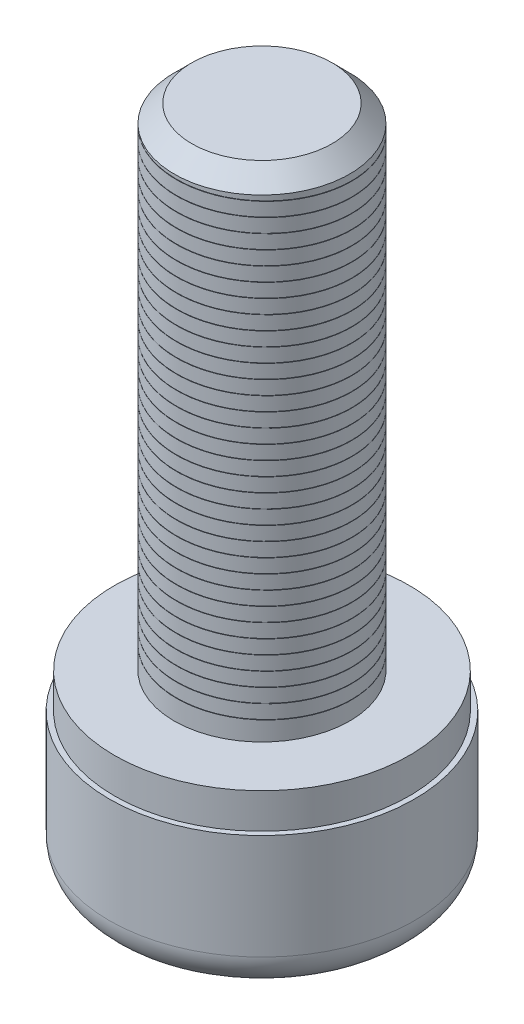
SolidWorks part; units mm, degrees
ref_plane "Спереди" through (0, 0, 0) normal (0, 0, 1) x (1, 0, 0)
ref_plane "Сверху" through (0, 0, 0) normal (0, 1, 0) x (1, 0, 0)
ref_plane "Справа" through (0, 0, 0) normal (1, 0, 0) x (0, 0, -1)
sketch "Эскиз1" plane through (0, 0, 0) normal (0, 1, 0) x (1, 0, 0)
  circle A0 centre (0, 0) radius 4.35
  dimension "D1" = 8.7
extrude "Бобышка-Вытянуть1" add sketch "Эскиз1" along normal blind 5
sketch "Эскиз2" plane through (0, 5, 0) normal (0, 1, 0) x (1, 0, 0)
  circle A0 centre (0, 0) radius 2.5
  dimension "D1" = 5
extrude "Бобышка-Вытянуть2" add sketch "Эскиз2" along normal blind 14
chamfer "Фаска1" distance 0.5 angle 45 1 edges at (0, 19, 2.5)
sketch "Эскиз3" plane through (0, 0, 0) normal (0, -1, 0) x (1, 0, 0)
  line L1 (1.9892, -1.1731) -> (2.0106, 1.1362)
  line L2 (2.0106, 1.1362) -> (0.0214, 2.3093)
  line L3 (0.0214, 2.3093) -> (-1.9892, 1.1731)
  line L4 (-1.9892, 1.1731) -> (-2.0106, -1.1362)
  line L5 (-2.0106, -1.1362) -> (-0.0214, -2.3093)
  line L6 (-0.0214, -2.3093) -> (1.9892, -1.1731)
  circle A0 centre (0, 0) radius 2 construction
  dimension "D1" = 4
extrude "Вырез-Вытянуть1" cut sketch "Эскиз3" against normal blind 2.5
fillet "Скругление1" radius 1 1 edges at (0, 0, 4.35)
sketch "Эскиз4" plane through (0, 5, 0) normal (0, 1, 0) x (1, 0, 0)
  circle A0 centre (0, 0) radius 4.2
  circle A1 centre (0, 0) radius 4.35
  dimension "D1" = 8.4
extrude "Вырез-Вытянуть3" cut sketch "Эскиз4" against normal blind 1
sketch "Эскиз7" plane through (0, 19, 0) normal (0, 1, 0) x (1, 0, 0)
  circle A0 centre (0, 0) radius 2.5
ref_plane "Плоскость2" through (0, 18.5, 0) normal (0, -1, 0) x (-1, 0, 0)
sketch "Эскиз8" plane through (0, 18.5, 0) normal (0, -1, 0) x (-1, 0, 0)
  circle A0 centre (0, 0) radius 2.5
curve "Спираль2" pitch 0.4 height 13.2 radius 2.5 left hand yes centre (0, 18.5, 0) axis (0, -1, 0) start towards (1, 0, 0)
sketch "Эскиз9" plane through (0, 18.5, 0) normal (0, -1, 0) x (-1, 0, 0)
  line L0 (2.6196, 0.3) -> (2.6196, -0.3)
  line L1 (2.6196, -0.3) -> (2.1, 0)
  line L2 (2.1, 0) -> (2.6196, 0.3)
  circle A0 centre (0, 0) radius 2.5 construction
  point P0 (2.5, 0)
  dimension "D1" = 0.6
  dimension "D2" = 0.4
sweep "Вырез-По траектории1" cut profiles "Эскиз9" path "Спираль2"
